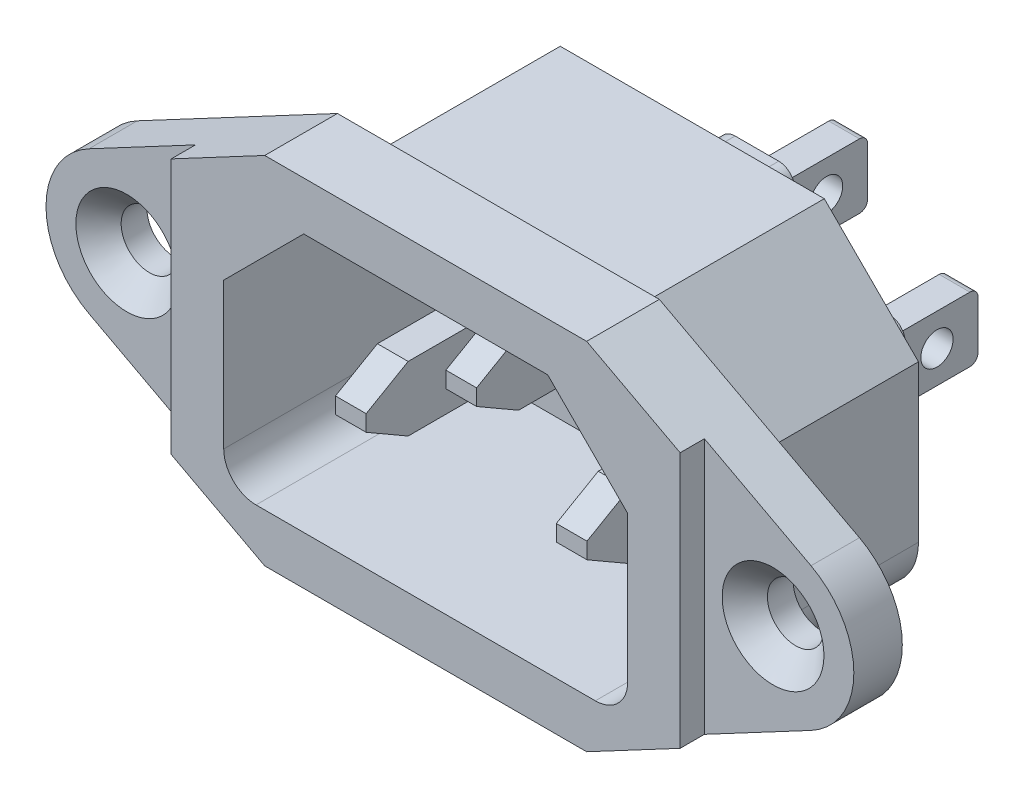
SolidWorks part; units mm, degrees
ref_plane "Front" through (0, 0, 0) normal (0, 0, 1) x (1, 0, 0)
ref_plane "Top" through (0, 0, 0) normal (0, 1, 0) x (1, 0, 0)
ref_plane "Right" through (0, 0, 0) normal (1, 0, 0) x (0, 0, -1)
sketch "Sketch1" plane through (0, 0, 0) normal (0, 0, 1) x (1, 0, 0)
  line L0 (0, 19.0426) -> (0, -21.8851) construction
  line L1 (-24.4226, 0) -> (32.5202, 0) construction
  line L2 (9.9623, 11) -> (22.3474, 4.4147)
  line L3 (0, 11) -> (9.9623, 11)
  line L4 (22.3474, -4.4147) -> (9.9623, -11)
  line L5 (0, -11) -> (9.9623, -11)
  line L6 (0, 8) -> (7.5503, 8)
  line L7 (7.5503, 8) -> (12.5, 3.0503)
  line L8 (12.5, 3.0503) -> (12.5, -6)
  line L9 (15.75, 7.9226) -> (15.75, -7.9226)
  line L10 (10.5, -8) -> (0, -8)
  line L11 (0, 11) -> (0, 8)
  line L12 (0, -8) -> (0, -11)
  line L13 (0, 9.5) -> (8.1716, 9.5)
  line L14 (8.1716, 9.5) -> (14, 3.6716)
  line L15 (14, 3.6716) -> (14, -6)
  line L16 (10.5, -9.5) -> (0, -9.5)
  line L17 (0, 8) -> (0, -8)
  arc A0 (22.3474, 4.4147) -> (22.3474, -4.4147) centre (20, 0) cw
  circle A1 centre (20, 0) radius 1.75
  arc A2 (12.5, -6) -> (10.5, -8) centre (10.5, -6) cw
  arc A3 (14, -6) -> (10.5, -9.5) centre (10.5, -6) cw
  dimension "D1" = 3.5
  dimension "D3" = 5
  dimension "D11" = 2
  dimension "D2" = 20
  dimension "D4" = 22
  dimension "D5" = 56
  dimension "D6" = 25
  dimension "D7" = 16
  dimension "D8" = 45
  dimension "D9" = 7
  dimension "D10" = 31.5
  dimension "D13" = 1.5
  dimension "D12" = 1.5
extrude "Boss-Extrude1" add sketch "Sketch1" against normal blind 3 contours L15 A3 L16 L12 L5 L4 L9 L2 L3 L11 L13 L14 | A3 L15 L14 L13 L11 L6 L7 L8 A2 L10 L12 L16 | A0 L2 L9 L4 A1 region at (12.7291, 9.2224, 0) region at (18.9625, 6.0067, 0) region at (4.0858, 9.264, 0)
extrude "Boss-Extrude2" add sketch "Sketch1<3>" along normal blind 1.5 contours A3 L15 L14 L13 L11 L6 L7 L8 A2 L10 L12 L16 | L15 A3 L16 L12 L5 L4 L9 L2 L3 L11 L13 L14 region at (12.7291, 9.2224, 0) region at (4.0858, 9.264, 0)
sketch "Sketch1<3>" plane through (0, 0, 0) normal (0, 0, 1) x (1, 0, 0) same geometry as "Sketch1"
extrude "Boss-Extrude3" add sketch "Sketch1<4>" against normal blind 15 contours A3 L15 L14 L13 L11 L6 L7 L8 A2 L10 L12 L16 region at (4.0858, 9.264, 0)
sketch "Sketch1<4>" plane through (0, 0, 0) normal (0, 0, 1) x (1, 0, 0) same geometry as "Sketch1"
sketch "Sketch2" plane through (0, 0, -15) normal (0, 0, -1) x (-1, 0, 0)
  line L0 (0, 9.5) -> (-8.1716, 9.5) construction
  line L1 (-8.1716, 9.5) -> (-14, 3.6716) construction
  line L2 (-14, 3.6716) -> (-14, -6) construction
  line L3 (-10.5, -9.5) -> (0, -9.5) construction
  line L4 (0, 9.5) -> (-8.1716, 9.5)
  line L5 (-8.1716, 9.5) -> (-14, 3.6716)
  line L6 (-14, 3.6716) -> (-14, -6)
  line L7 (-10.5, -9.5) -> (0, -9.5)
  line L8 (0, 9.5) -> (0, -9.5)
  arc A0 (-14, -6) -> (-10.5, -9.5) centre (-10.5, -6) ccw construction
  arc A1 (-14, -6) -> (-10.5, -9.5) centre (-10.5, -6) ccw
extrude "Boss-Extrude4" add sketch "Sketch2" against normal blind 2.5
chamfer "Chamfer2" distance 1.4 angle 45 1 edges at (21.75, 0, 0)
mirror "Mirror1" about plane through (0, 0, 0) normal (1, 0, 0) of bodies 104
sketch "Sketch4" plane through (0, 0, -15) normal (0, 0, -1) x (-1, 0, 0)
  line L0 (-6.8345, 0) -> (6.9295, 0) construction
  line L1 (0, 5.3419) -> (0, -4.5033) construction
  line L2 (-6.8342, -2.4) -> (6.8342, -2.4) construction
  line L3 (-10.5, -9.5) -> (10.5, -9.5) construction
  line L4 (8.1716, 9.5) -> (-8.1716, 9.5) construction
  point P7 (0, -2.4)
  line B0 (0, 6.1) -> (0, -1.3) construction
  line B1 (-1.35, 6.1) -> (1.35, 6.1)
  line B2 (-2.35, 5.1) -> (-2.35, -0.3)
  line B3 (-1.35, -1.3) -> (1.35, -1.3)
  line B4 (2.35, 5.1) -> (2.35, -0.3)
  line B5 (-0.95, 4.4) -> (0.95, 4.4)
  line B6 (-0.95, 4.4) -> (-0.95, 0.4)
  line B7 (-0.95, 0.4) -> (0.95, 0.4)
  line B8 (0.95, 4.4) -> (0.95, 0.4)
  line B9 (-0.95, 4.4) -> (0.95, 0.4) construction
  line B10 (-0.95, 0.4) -> (0.95, 4.4) construction
  arc B11 (1.35, 6.1) -> (2.35, 5.1) centre (1.35, 5.1) cw
  arc B12 (-1.35, 6.1) -> (-2.35, 5.1) centre (-1.35, 5.1) ccw
  arc B13 (-2.35, -0.3) -> (-1.35, -1.3) centre (-1.35, -0.3) ccw
  arc B14 (1.35, -1.3) -> (2.35, -0.3) centre (1.35, -0.3) ccw
  line B15 (-6.8342, 1.3) -> (-6.8342, -6.1) construction
  line B16 (-8.1842, 1.3) -> (-5.4842, 1.3)
  line B17 (-9.1842, 0.3) -> (-9.1842, -5.1)
  line B18 (-8.1842, -6.1) -> (-5.4842, -6.1)
  line B19 (-4.4842, 0.3) -> (-4.4842, -5.1)
  line B20 (-7.7842, -0.4) -> (-5.8842, -0.4)
  line B21 (-7.7842, -0.4) -> (-7.7842, -4.4)
  line B22 (-7.7842, -4.4) -> (-5.8842, -4.4)
  line B23 (-5.8842, -0.4) -> (-5.8842, -4.4)
  line B24 (-7.7842, -0.4) -> (-5.8842, -4.4) construction
  line B25 (-7.7842, -4.4) -> (-5.8842, -0.4) construction
  arc B26 (-5.4842, 1.3) -> (-4.4842, 0.3) centre (-5.4842, 0.3) cw
  arc B27 (-8.1842, 1.3) -> (-9.1842, 0.3) centre (-8.1842, 0.3) ccw
  arc B28 (-9.1842, -5.1) -> (-8.1842, -6.1) centre (-8.1842, -5.1) ccw
  arc B29 (-5.4842, -6.1) -> (-4.4842, -5.1) centre (-5.4842, -5.1) ccw
  line B30 (6.8342, 1.3) -> (6.8342, -6.1) construction
  line B31 (5.4842, 1.3) -> (8.1842, 1.3)
  line B32 (4.4842, 0.3) -> (4.4842, -5.1)
  line B33 (5.4842, -6.1) -> (8.1842, -6.1)
  line B34 (9.1842, 0.3) -> (9.1842, -5.1)
  line B35 (5.8842, -0.4) -> (7.7842, -0.4)
  line B36 (5.8842, -0.4) -> (5.8842, -4.4)
  line B37 (5.8842, -4.4) -> (7.7842, -4.4)
  line B38 (7.7842, -0.4) -> (7.7842, -4.4)
  line B39 (5.8842, -0.4) -> (7.7842, -4.4) construction
  line B40 (5.8842, -4.4) -> (7.7842, -0.4) construction
  arc B41 (8.1842, 1.3) -> (9.1842, 0.3) centre (8.1842, 0.3) cw
  arc B42 (5.4842, 1.3) -> (4.4842, 0.3) centre (5.4842, 0.3) ccw
  arc B43 (4.4842, -5.1) -> (5.4842, -6.1) centre (5.4842, -5.1) ccw
  arc B44 (8.1842, -6.1) -> (9.1842, -5.1) centre (8.1842, -5.1) ccw
  dimension "D1" = 3.4
  dimension "D2" = 3.4
sketch_block_instance "Block1-1"
sketch_block "Block1" parameters "D1"=1, "D2"=7.4, "D3"=4.7, "D4"=4, "D5"=1.9
sketch_block_instance "Block1-2"
sketch_block_instance "Block1-3"
extrude "Boss-Extrude5" add sketch "Sketch4" along normal blind 4
extrude "Cut-Extrude1" cut sketch "Sketch4<2>" against normal through all contours B23 B20 B21 B22 | B8 B5 B6 B7 | B38 B35 B36 B37 region at (0, 2.4, -15) region at (6.8342, -2.4, -15) region at (-6.8342, -2.4, -15)
sketch "Sketch4<2>" plane through (0, 0, -15) normal (0, 0, -1) x (-1, 0, 0) same geometry as "Sketch4"
extrude "Boss-Extrude6" add sketch "Sketch4<3>" along normal blind 9.9 and the other way blind 14.3 separate body contours B23 B20 B21 B22 | B8 B5 B6 B7 | B38 B35 B36 B37 region at (0, 2.4, -15) region at (6.8342, -2.4, -15) region at (-6.8342, -2.4, -15)
sketch "Sketch4<3>" plane through (0, 0, -15) normal (0, 0, -1) x (-1, 0, 0) same geometry as "Sketch4"
fillet "Fillet1" radius 0.5 2 edges at (6.8342, -0.4, -24.9) (6.8342, -4.4, -24.9)
fillet "Fillet2" radius 0.5 2 edges at (0, 4.4, -24.9) (0, 0.4, -24.9)
fillet "Fillet3" radius 0.5 2 edges at (-6.8342, -0.4, -24.9) (-6.8342, -4.4, -24.9)
sketch "Sketch5" plane through (0, 0, 0) normal (1, 0, 0) x (0, 0, -1)
  line L0 (24.9, 2.4) -> (22.36, 2.4) construction
  line L1 (24.9, 3.9) -> (24.9, 0.9) construction
  line L2 (24.9, -2.4) -> (22.36, -2.4) construction
  line L3 (24.9, -0.9) -> (24.9, -3.9) construction
  circle A0 centre (22.36, 2.4) radius 1
  circle A1 centre (22.36, -2.4) radius 1
  dimension "D1" = 2
  dimension "D2" = 2.54
extrude "Cut-Extrude2" cut sketch "Sketch5" against normal through all and the other way through all
chamfer "Chamfer3" distance 1.5 angle 60 2 edges at (-6.8342, -0.4, -0.7) (-6.8342, -4.4, -0.7) first distance on face at (-6.8342, -2.4, -0.7)
chamfer "Chamfer4" distance 1.5 angle 60 2 edges at (0, 4.4, -0.7) (0, 0.4, -0.7) first distance on face at (0, 2.4, -0.7)
chamfer "Chamfer5" distance 1.5 angle 60 2 edges at (6.8342, -0.4, -0.7) (6.8342, -4.4, -0.7) first distance on face at (6.8342, -2.4, -0.7)
